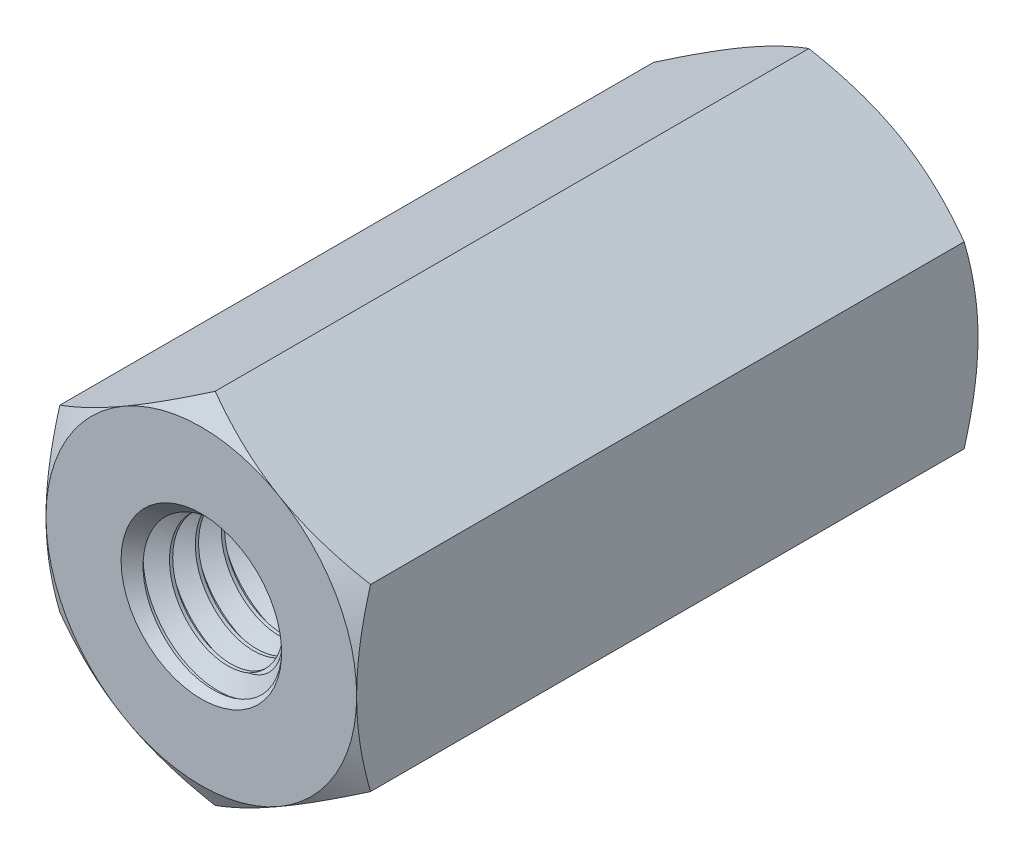
SolidWorks part; units mm, degrees
ref_plane "Front Plane" through (0, 0, 0) normal (0, 0, 1) x (1, 0, 0)
ref_plane "Top Plane" through (0, 0, 0) normal (0, 1, 0) x (1, 0, 0)
ref_plane "Right Plane" through (0, 0, 0) normal (1, 0, 0) x (0, 0, -1)
sketch "Sketch3" plane through (0, 0, 0) normal (1, 0, 0) x (0, 0, -1)
  line L0 (-6, 0) -> (6, 0) construction
  line L1 (0, 3) -> (0, -3) construction
  line L2 (-6, 1.5) -> (-6, -1.5) construction
  line L3 (-6, 3) -> (6, 3) construction
  point P2 (-3.525, 0)
  point P3 (3.525, 0)
  dimension "D1" = 9.525
  dimension "Length" = 12
  dimension "Min Thread Length" = 9.525
  dimension "D2" = 12
  dimension "Thread Dia" = 3
  dimension "Hex" = 6
sketch "Sketch1" plane through (0, 0, 0) normal (0, 0, 1) x (1, 0, 0)
  line L1 (0, 3.4641) -> (-3, 1.7321)
  line L2 (-3, 1.7321) -> (-3, -1.7321)
  line L3 (-3, -1.7321) -> (0, -3.4641)
  line L4 (0, -3.4641) -> (3, -1.7321)
  line L5 (3, -1.7321) -> (3, 1.7321)
  line L6 (3, 1.7321) -> (0, 3.4641)
  circle A0 centre (0, 0) radius 3 construction
  circle A1 centre (0, 0) radius 1.5
extrude "Extrude1" add sketch "Sketch1" along normal up to vertex (6 mm away) and the other way up to vertex (6 mm away) up to point (0, 0, 6) other way up to point (0, 0, -6)
sketch "Sketch11" plane through (0, 0, -6) normal (0, 0, -1) x (-1, 0, 0)
  circle A0 centre (0, 0) radius 1.5 construction
  circle A1 centre (0, 0) radius 1.5
curve "Helix/Spiral1" pitch 0.5 height 12.5 turns 25 parameters "Pitch"=0.5
sketch "Sketch12" plane through (0, 0, 0) normal (1, 0, 0) x (0, 0, -1)
  line L0 (6.4375, 1.5) -> (6, 1.5)
  line L1 (6.4375, 1.5) -> (6.25, 1.1752)
  line L2 (6.25, 1.1752) -> (6.1875, 1.1752)
  line L3 (6.1875, 1.1752) -> (6, 1.5)
  line L4 (6.2188, 1.1752) -> (6.2188, 1.5) construction
  line L5 (6.3438, 1.3376) -> (6.0938, 1.3376) construction
  dimension "D1" = 0.0625
  dimension "D2" = 0.25
  dimension "D3" = 60
sweep "Sweep1" add profiles "Sketch12" path "Helix/Spiral1"
sketch "Sketch6" plane through (0, 0, -6) normal (0, 0, -1) x (-1, 0, 0)
  line L6 (0, 3.4641) -> (-3, 1.7321)
  line L7 (-3, 1.7321) -> (-3, -1.7321)
  line L8 (-3, -1.7321) -> (0, -3.4641)
  line L9 (0, -3.4641) -> (3, -1.7321)
  line L10 (3, -1.7321) -> (3, 1.7321)
  line L11 (3, 1.7321) -> (0, 3.4641)
  line L12 (0, 3.4641) -> (-3, 1.7321)
  line L13 (-3, 1.7321) -> (-3, -1.7321)
  line L14 (-3, -1.7321) -> (0, -3.4641)
  line L15 (0, -3.4641) -> (3, -1.7321)
  line L16 (3, -1.7321) -> (3, 1.7321)
  line L17 (3, 1.7321) -> (0, 3.4641)
  dimension "D1" = 0
extrude "Extrude2" cut sketch "Sketch6" along normal through all
sketch "Sketch7" plane through (0, 0, -6) normal (0, 0, -1) x (-1, 0, 0)
  circle A2 centre (0, 0) radius 1.5508
  circle A3 centre (0, 0) radius 1.5508
  dimension "D1" = 0.0508
extrude "Extrude3" cut sketch "Sketch7" against normal through all draft 43
sketch "Sketch8" plane through (0, 0, -6) normal (0, 0, -1) x (-1, 0, 0)
  circle A0 centre (0, 0) radius 3 construction
  circle A1 centre (0, 0) radius 3
extrude "Extrude4" cut sketch "Sketch8" against normal through all draft 60 flip side to cut
mirror "Mirror1" about plane through (0, 0, 0) normal (0, 0, 1) of "Extrude2", "Extrude3", "Extrude4"
sketch "Sketch9" [suppressed] plane through (0, 0, 0) normal (1, 0, 0) x (0, 0, -1)
  line L1 (-19.7, 1.5508) -> (19.7, 1.5508)
  line L2 (-19.7, 1.5508) -> (-19.7, 0)
  line L3 (-19.7, 0) -> (19.7, 0)
  line L4 (19.7, 1.5508) -> (19.7, 0)
  line L7 (-26, 0) -> (26, 0) construction
revolve "Revolve" [suppressed] add sketch "Sketch9" angle 360 about L0
sketch "Sketch10" [suppressed] plane through (0, 0, 0) normal (1, 0, 0) x (0, 0, -1)
  line L0 (26, 1.5) -> (19.7, 1.5)
  line L1 (-26, 1.5) -> (-19.7, 1.5)
  line L2 (19.7, 1.5) -> (19.7, -1.5)
  line L3 (-26, -1.5508) -> (-19.7, -1.5508)
  line L4 (-19.7, 1.5) -> (-19.7, -1.5508)
  line L5 (19.7, -1.5) -> (26, -1.5)
equation "\"D1@Sketch3\" = \"Min Thread Length@Sketch3\""
equation "\"D3@Helix/Spiral1\" = \"Length@Sketch3\"+\"Pitch@Helix/Spiral1\""
equation "\"D1@Sketch12\" = \"Pitch@Helix/Spiral1\"*.125"
equation "\"D2@Sketch12\" = \"Pitch@Helix/Spiral1\"*.5"
equation "\"D2@Sketch3\" = \"Length@Sketch3\""
